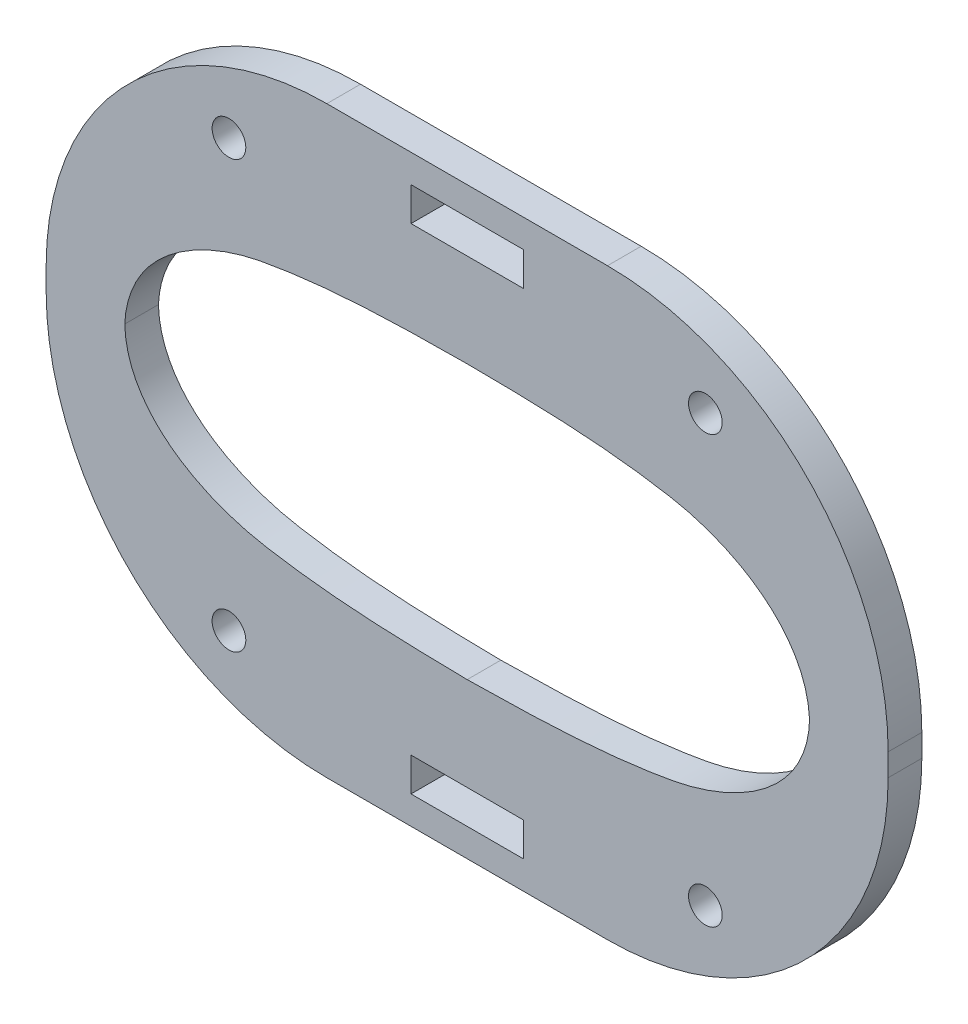
SolidWorks part; units mm, degrees
material "MDF"
ref_plane "Plano frontal" through (0, 0, 0) normal (0, 0, 1) x (1, 0, 0)
ref_plane "Plano superior" through (0, 0, 0) normal (0, 1, 0) x (1, 0, 0)
ref_plane "Plano direito" through (0, 0, 0) normal (1, 0, 0) x (0, 0, -1)
sketch "Esboço1" plane through (0, 0, 0) normal (0, 0, 1) x (1, 0, 0)
  line L0 (37.5, 0) -> (-37.5, 0) construction
  line L5 (12.5, 26) -> (-12.5, 26)
  line L6 (37.5, 1) -> (37.5, -1)
  line L7 (12.5, -26) -> (-12.5, -26)
  line L8 (-37.5, 1) -> (-37.5, -1)
  line L13 (37.5, 26) -> (-37.5, -26) construction
  line L14 (37.5, -26) -> (-37.5, 26) construction
  line L27 (0, -12.1787) -> (0, 12.1787) construction
  line L28 (30.5, 0) -> (-30.5, 0) construction
  line L29 (5, -23.5) -> (-5, -23.5)
  line L30 (5, -23.5) -> (5, -20.5)
  line L31 (5, -20.5) -> (-5, -20.5)
  line L32 (-5, -23.5) -> (-5, -20.5)
  line L33 (5, -23.5) -> (-5, -20.5) construction
  line L34 (5, -20.5) -> (-5, -23.5) construction
  line L35 (5, 20.5) -> (-5, 23.5) construction
  line L36 (5, 23.5) -> (-5, 20.5) construction
  line L37 (-5, 23.5) -> (-5, 20.5)
  line L38 (5, 20.5) -> (-5, 20.5)
  line L39 (5, 23.5) -> (5, 20.5)
  line L40 (5, 23.5) -> (-5, 23.5)
  line L42 (0, -26) -> (0, 26) construction
  arc A0 (-12.5, -26) -> (-37.5, -1) centre (-12.5, -1) cw
  arc A1 (-12.5, 26) -> (-37.5, 1) centre (-12.5, 1) ccw
  arc A2 (12.5, 26) -> (37.5, 1) centre (12.5, 1) cw
  arc A3 (37.5, -1) -> (12.5, -26) centre (12.5, -1) cw
  circle A4 centre (21.2178, -19) radius 1.5
  circle A5 centre (-21.2178, -19) radius 1.5
  circle A6 centre (21.2178, 19) radius 1.5
  circle A7 centre (-21.2178, 19) radius 1.5
  circle A8 centre (21.2178, -19) radius 5 construction
  spline S0 degree 3 poles (0, 12.1787) (-6.0803, 12.1429) (-12.1923, 12.0291) (-24.1494, 9.8711) (-30.2094, 6.1156) (-30.5, 0) knots 0 0 0 0 0.5 0.5 1 1 1 1
  spline S1 degree 3 poles (30.5, 0) (30.3478, -6.1089) (24.1602, -9.7683) (12.1875, -11.9292) (6.0823, -12.0841) (0, -12.1787) knots 0 0 0 0 0.5 0.5 1 1 1 1
  spline S2 degree 3 poles (0, 12.1787) (6.0803, 12.1429) (12.1923, 12.0291) (24.1494, 9.8711) (30.2094, 6.1156) (30.5, 0) knots 0 0 0 0 0.5 0.5 1 1 1 1
  spline S3 degree 3 poles (-30.5, 0) (-30.3478, -6.1089) (-24.1602, -9.7683) (-12.1875, -11.9292) (-6.0823, -12.0841) (0, -12.1787) knots 0 0 0 0 0.5 0.5 1 1 1 1
  point P0 (0, 0)
  point P1 (0, 0)
  point P6 (0, -22)
  point P18 (0, 22)
  point P45 (0, 0)
  point P46 (24.9462, -19)
  dimension "D5" = 61
  dimension "D6" = 25
  dimension "D8" = 3
  dimension "D9" = 7
  dimension "D10" = 24.3575
  dimension "D11" = 10
  dimension "D1" = 52
  dimension "D2" = 75
  dimension "D3" = 10
  dimension "D4" = 3
  dimension "D7" = 4
extrude "Ressalto-extrusão1" add sketch "Esboço1" along normal blind 3
